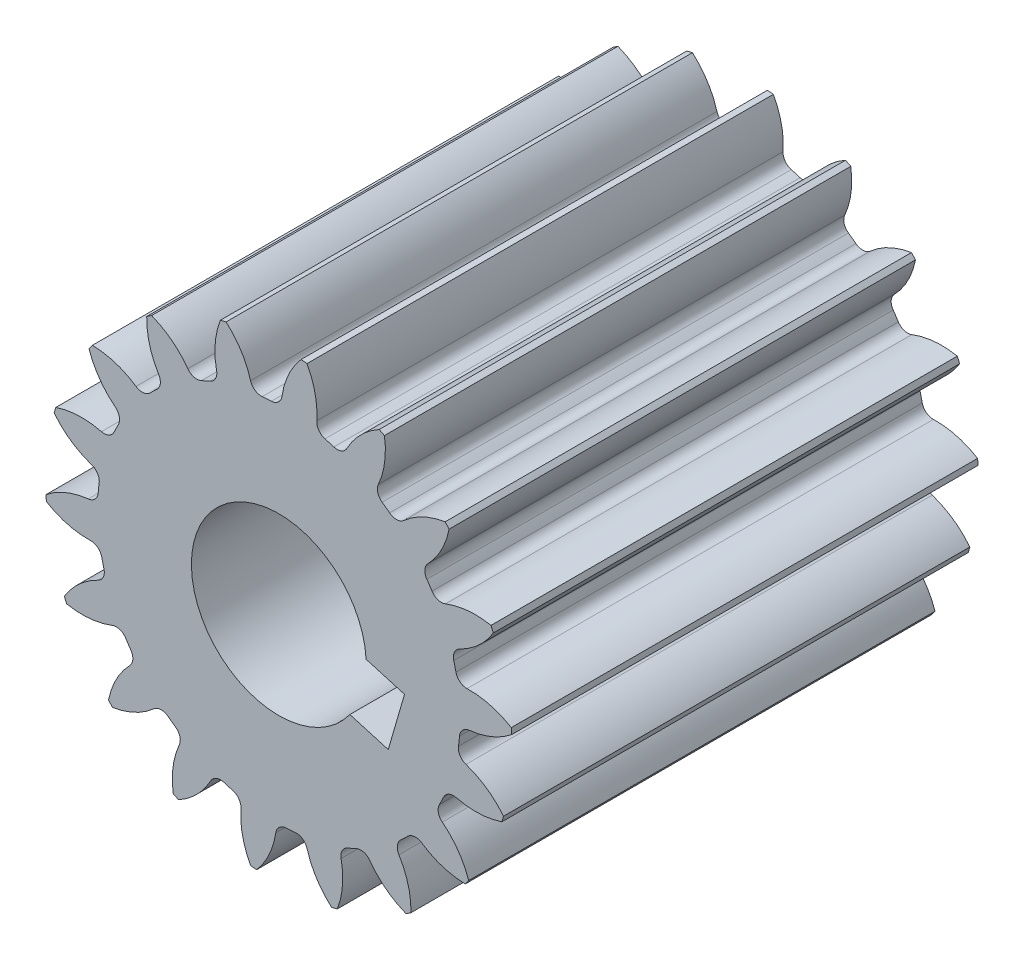
SolidWorks part; units mm, degrees
ref_plane "Front" through (0, 0, 0) normal (0, 0, 1) x (1, 0, 0)
ref_plane "Top" through (0, 0, 0) normal (0, 1, 0) x (1, 0, 0)
ref_plane "Right" through (0, 0, 0) normal (1, 0, 0) x (0, 0, -1)
sketch "Sketch3" plane through (0, 0, 0) normal (0, 0, 1) x (1, 0, 0)
  circle A0 centre (0, 0) radius 20
  dimension "od" = 40
extrude "gearBody" add sketch "Sketch3" along normal blind 40
sketch "Sketch2" plane through (0, 0, 0) normal (0, 0, 1) x (1, 0, 0)
  line L0 (0, 0) -> (15.6269, 6.4729) construction
  line L1 (20.3029, -7.0972) -> (0, 0) construction
  line L2 (0, 0) -> (36.3143, 0) construction
  line L3 (18, -0.0406) -> (17.5878, -3.8298) construction
  line L5 (17.7939, -1.9352) -> (0, 0) construction
  line L7 (0, 0) -> (16.9145, 0) construction
  arc A0 (16.9111, -0.3395) -> (16.5887, -3.3039) centre (0, 0) ccw construction
  arc A1 (19.9713, 1.0707) -> (19.2742, -5.339) centre (0, 0) ccw construction
  arc A2 (18, -0.0406) -> (17.5878, -3.8298) centre (0, 0) ccw construction
  arc A3 (15.4101, -2.075) -> (15.4959, -1.2863) centre (0, 0) ccw
  arc A4 (20.3029, -7.0972) -> (16.0509, -3.1006) centre (13.8701, -9.6809) ccw
  arc A5 (20.3029, -7.0972) -> (21.354, 2.5667) centre (0, 0) ccw
  arc A6 (21.354, 2.5667) -> (16.3422, -0.4224) centre (15.6269, 6.4729) cw
  arc A7 (15.4959, -1.2863) -> (16.3422, -0.4224) centre (16.44, -1.3647) cw
  arc A8 (16.0509, -3.1006) -> (15.4101, -2.075) centre (16.349, -2.2014) cw
  point P6 (21.354, 2.5667)
  point P22 (20.3029, -7.0972)
  dimension "baseDia" = 33.8289
  dimension "od" = 40
  dimension "pd" = 36
  dimension "rd" = 31.0984
  dimension "rFillet" = 0.9473
  dimension "pointX" = 21.354
  dimension "pointY" = 2.5667
  dimension "CTT" = 3.7892
  dimension "flankCenterAngle" = 22.5
extrude "toothCut" cut sketch "Sketch2" along normal through all
pattern_circular "CirPattern1" count 18 over 360 about axis through (0, 0, 40) along (0, 0, -1) of "toothCut"
ref_axis "toothSpace" through (0, 0, 0) along (0.9941, -0.1081, 0)
ref_axis "Axis2" through (19.2052, -5.5822, 0) along (-0.9603, 0.2791, 0)
sketch "hub1Dia" plane through (0, 0, 0) normal (0, 0, -1) x (-1, 0, 0)
  circle A0 centre (0, 0) radius 0.5
  dimension "hub1Dia" = 1
sketch "hub2Dia" plane through (0, 0, 40) normal (0, 0, 1) x (1, 0, 0)
  circle A0 centre (0, 0) radius 0.5
  dimension "hub2dia" = 1
sketch "boreDia" plane through (0, 0, 0) normal (0, 0, 1) x (1, 0, 0)
  circle A0 centre (0, 0) radius 7.5
  dimension "boreDia" = 15
extrude "bore" cut sketch "boreDia" against normal mid plane 25400
sketch "kwy1sketch" plane through (0, 0, 0) normal (0, 0, 1) x (1, 0, 0)
  line L0 (-5.1537, 1.498) -> (0, 0) construction
  line L1 (10.7805, -0.53) -> (9.385, -5.3313)
  line L2 (9.385, -5.3313) -> (3.3833, -3.5869)
  line L3 (10.7805, -0.53) -> (4.7789, 1.2144)
  line L4 (3.3833, -3.5869) -> (0, 0)
  line L5 (0, 0) -> (4.7789, 1.2144)
  line L6 (0, 0) -> (15.458, -1.6812) construction
  line L7 (10.0827, -2.9306) -> (0, 0) construction
  arc A7 (15.4101, -2.075) -> (15.4959, -1.2863) centre (0, 0) ccw construction
  point P9 (10.0827, -2.9306)
  point P13 (-0.8597, 0.2499)
  dimension "kwy1width" = 5
  dimension "kwy1depth" = 10.5
  dimension "kwy1angle" = 10
  dimension "kwy1Depth2" = 6.25
extrude "kwy1" cut sketch "kwy1sketch" against normal mid plane 12700
sketch "kwy2sketch" plane through (0, 0, 0) normal (0, 0, 1) x (1, 0, 0)
  line L0 (15.458, -1.6812) -> (0, 0) construction
  line L1 (0, 0) -> (-3.2503, -1.7863) construction
  line L2 (7.9977, 7.2482) -> (10.406, 2.8664)
  line L3 (10.406, 2.8664) -> (4.9287, -0.1439)
  line L4 (7.9977, 7.2482) -> (2.5204, 4.2379)
  line L5 (4.9287, -0.1439) -> (0, 0)
  line L6 (0, 0) -> (2.5204, 4.2379)
  arc A2 (15.4101, -2.075) -> (15.4959, -1.2863) centre (0, 0) ccw construction
  point P10 (9.2018, 5.0573)
  dimension "kwy2angle" = 35
  dimension "kwy2Width" = 5
  dimension "kwy2depth" = 10.5
  dimension "kwy2Depth2" = 6.25
sketch "kwy3sketch" plane through (0, 0, 0) normal (0, 0, 1) x (1, 0, 0)
  line L0 (15.458, -1.6812) -> (0, 0) construction
  line L1 (0, 0) -> (-0.7489, -2.5765) construction
  line L2 (0.53, 10.7805) -> (5.3313, 9.385)
  line L3 (5.3313, 9.385) -> (3.5869, 3.3833)
  line L4 (0.53, 10.7805) -> (-1.2144, 4.7789)
  line L5 (3.5869, 3.3833) -> (0, 0)
  line L6 (-1.2144, 4.7789) -> (0, 0)
  point P10 (2.9306, 10.0827)
  dimension "kwy3angle" = 80
  dimension "kwy3depth" = 10.5
  dimension "kwy3width" = 5
  dimension "kwy3Depth2" = 6.25
sketch "kwy4sketch" plane through (0, 0, 0) normal (0, 0, 1) x (1, 0, 0)
  line L0 (15.458, -1.6812) -> (0, 0) construction
  line L1 (0, 0) -> (1.0105, -1.8386) construction
  line L2 (-2.8664, 10.406) -> (-7.2482, 7.9977)
  line L3 (-7.2482, 7.9977) -> (-4.2379, 2.5204)
  line L4 (-4.2379, 2.5204) -> (0, 0)
  line L5 (0.1439, 4.9287) -> (0, 0)
  line L6 (-2.8664, 10.406) -> (0.1439, 4.9287)
  point P15 (-5.0573, 9.2018)
  dimension "kwy4angle" = 125
  dimension "kwy4depth" = 10.5
  dimension "kwy4width" = 5
  dimension "kwy4Depth2" = 6.25
sketch "kwy5sketch" plane through (0, 0, 0) normal (0, 0, 1) x (1, 0, 0)
  line L0 (15.458, -1.6812) -> (0, 0) construction
  line L1 (0, 0) -> (1.7302, -0.5029) construction
  line L2 (-9.385, 5.3313) -> (-10.7805, 0.53)
  line L3 (-10.7805, 0.53) -> (-4.7789, -1.2144)
  line L4 (-9.385, 5.3313) -> (-3.3833, 3.5869)
  line L5 (-4.7789, -1.2144) -> (0, 0)
  line L6 (-3.3833, 3.5869) -> (0, 0)
  point P10 (-10.0827, 2.9306)
  dimension "kwy5width" = 5
  dimension "kwy5depth" = 10.5
  dimension "kwy5angle" = 170
  dimension "kwy5Depth2" = 6.25
sketch "kwy6sketch" plane through (0, 0, 0) normal (0, 0, 1) x (1, 0, 0)
  line L0 (15.458, -1.6812) -> (0, 0) construction
  line L1 (0, 0) -> (1.5778, 0.8671) construction
  line L2 (-10.406, -2.8664) -> (-7.9977, -7.2482)
  line L3 (-7.9977, -7.2482) -> (-2.5204, -4.2379)
  line L4 (-10.406, -2.8664) -> (-4.9287, 0.1439)
  line L5 (-2.5204, -4.2379) -> (0, 0)
  line L6 (-4.9287, 0.1439) -> (0, 0)
  point P10 (-9.2018, -5.0573)
  dimension "kwy6angle" = 215
  dimension "kwy6width" = 5
  dimension "kwy6depth" = 10.5
  dimension "kwy6Depth2" = 6.25
sketch "kwy7sketch" plane through (0, 0, 0) normal (0, 0, 1) x (1, 0, 0)
  line L0 (15.458, -1.6812) -> (0, 0) construction
  line L1 (0, 0) -> (0.563, 1.9368) construction
  line L2 (-5.3313, -9.385) -> (-0.53, -10.7805)
  line L3 (-5.3313, -9.385) -> (-3.5869, -3.3833)
  line L4 (-0.53, -10.7805) -> (1.2144, -4.7789)
  line L5 (-3.5869, -3.3833) -> (0, 0)
  line L6 (1.2144, -4.7789) -> (0, 0)
  point P10 (-2.9306, -10.0827)
  dimension "kwy7angle" = 80
  dimension "kwy7width" = 5
  dimension "kwy7depth" = 10.5
  dimension "kwy7angle1" = 260
  dimension "kwy7Depth2" = 6.25
sketch "kwy8sketch" plane through (0, 0, 0) normal (0, 0, 1) x (1, 0, 0)
  line L0 (15.458, -1.6812) -> (0, 0) construction
  line L1 (0, 0) -> (-0.8631, 1.5704) construction
  line L2 (2.8664, -10.406) -> (7.2482, -7.9977)
  line L3 (7.2482, -7.9977) -> (4.2379, -2.5204)
  line L4 (2.8664, -10.406) -> (-0.1439, -4.9287)
  line L5 (4.2379, -2.5204) -> (0, 0)
  line L6 (-0.1439, -4.9287) -> (0, 0)
  point P10 (5.0573, -9.2018)
  dimension "kwy8angle" = 305
  dimension "kwy8width" = 5
  dimension "kwy8depth" = 10.5
  dimension "kwy8Depth2" = 6.25
sketch "centerLine" plane through (0, 0, 0) normal (0, 1, 0) x (1, 0, 0)
  line L0 (0, 36.4807) -> (0, -59.6309) construction
ref_plane "CB1plane" through (0, 0, 0) normal (0, 0, -1) x (-1, 0, 0)
sketch "CB1diameter" plane through (0, 0, 0) normal (0, 0, -1) x (-1, 0, 0)
  circle A0 centre (0, 0) radius 0.5
  dimension "CB1diameter" = 1
ref_plane "CB2plane" through (0, 0, 40) normal (0, 0, 1) x (1, 0, 0)
sketch "CB2diameter" plane through (0, 0, 40) normal (0, 0, 1) x (1, 0, 0)
  circle A0 centre (0, 0) radius 0.5
  dimension "CB2diameter" = 1
ref_axis "Axis1" through (0, 0, 50) along (0, 0, -1)
sketch3d "3DSketch1" plane through (0, 0, 0) normal (0, 0, 1) x (1, 0, 0)
